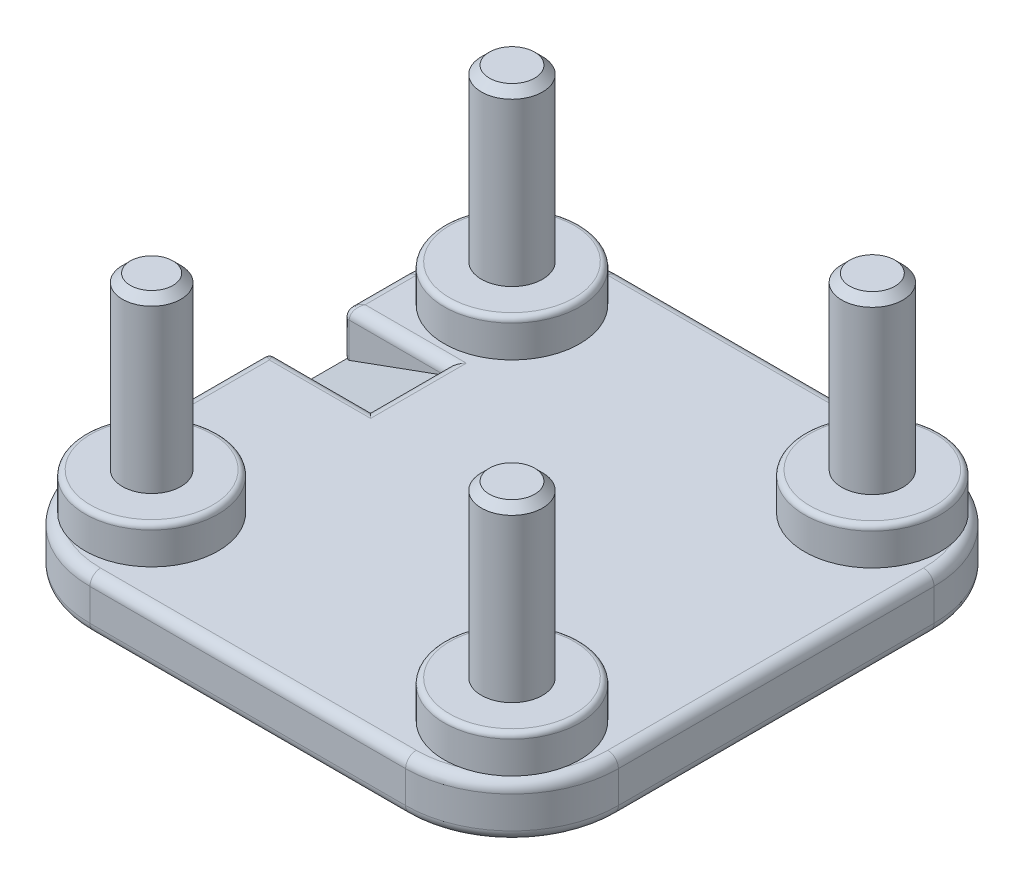
SolidWorks part; units mm, degrees
ref_plane "Front Plane" through (0, 0, 0) normal (0, 0, 1) x (1, 0, 0)
ref_plane "Top Plane" through (0, 0, 0) normal (0, 1, 0) x (1, 0, 0)
ref_plane "Right Plane" through (0, 0, 0) normal (1, 0, 0) x (0, 0, -1)
sketch "Sketch1" plane through (0, 0, 0) normal (0, 1, 0) x (1, 0, 0)
  line L1 (0.1721, 16.4036) -> (49.8471, 16.4036)
  line L2 (0.1721, 16.4036) -> (0.1721, 66.0786)
  line L3 (0.1721, 66.0786) -> (49.8471, 66.0786)
  line L4 (49.8471, 16.4036) -> (49.8471, 66.0786)
  line L8 (14.7548, 29.4959) -> (35.2548, 29.4959)
  line L9 (13.2548, 51.4959) -> (13.2548, 30.9959)
  line L10 (35.2548, 52.9959) -> (14.7548, 52.9959)
  line L11 (36.7548, 30.9959) -> (36.7548, 51.4959)
  line L12 (14.7548, 29.4959) -> (35.2548, 29.4959) construction
  line L13 (13.2548, 51.4959) -> (13.2548, 30.9959) construction
  line L14 (35.2548, 52.9959) -> (14.7548, 52.9959) construction
  line L15 (36.7548, 30.9959) -> (36.7548, 51.4959) construction
  line L16 (14.0048, 34.5935) -> (18.0048, 34.5935)
  line L17 (14.0048, 47.8007) -> (14.0048, 34.5935)
  line L18 (18.0048, 47.8007) -> (14.0048, 47.8007)
  line L19 (18.0048, 34.5935) -> (18.0048, 47.8007)
  line L20 (14.0048, 34.5935) -> (18.0048, 34.5935) construction
  line L21 (14.0048, 47.8007) -> (14.0048, 34.5935) construction
  line L22 (18.0048, 47.8007) -> (14.0048, 47.8007) construction
  line L23 (18.0048, 34.5935) -> (18.0048, 47.8007) construction
  line L24 (32.0048, 34.5935) -> (36.0048, 34.5935)
  line L25 (36.0048, 34.5935) -> (36.0048, 47.8007)
  line L26 (36.0048, 47.8007) -> (32.0048, 47.8007)
  line L27 (32.0048, 47.8007) -> (32.0048, 34.5935)
  line L28 (32.0048, 34.5935) -> (36.0048, 34.5935) construction
  line L29 (36.0048, 34.5935) -> (36.0048, 47.8007) construction
  line L30 (36.0048, 47.8007) -> (32.0048, 47.8007) construction
  line L31 (32.0048, 47.8007) -> (32.0048, 34.5935) construction
  line L32 (30.1074, 36.5249) -> (31.1807, 36.5249)
  line L33 (30.1074, 45.8309) -> (30.1074, 36.5249)
  line L34 (31.1807, 45.8309) -> (30.1074, 45.8309)
  line L35 (31.1807, 36.5249) -> (31.1807, 45.8309)
  line L36 (30.1074, 36.5249) -> (31.1807, 36.5249) construction
  line L37 (30.1074, 45.8309) -> (30.1074, 36.5249) construction
  line L38 (31.1807, 45.8309) -> (30.1074, 45.8309) construction
  line L39 (31.1807, 36.5249) -> (31.1807, 45.8309) construction
  line L40 (18.0048, 37.8287) -> (22.2111, 37.8287)
  line L41 (18.0048, 44.6472) -> (18.0048, 37.8287)
  line L42 (22.2111, 44.6472) -> (18.0048, 44.6472)
  line L43 (22.2111, 37.8287) -> (22.2111, 44.6472)
  line L44 (18.0048, 37.8287) -> (22.2111, 37.8287) construction
  line L45 (18.0048, 44.6472) -> (18.0048, 37.8287) construction
  line L46 (22.2111, 44.6472) -> (18.0048, 44.6472) construction
  line L47 (22.2111, 37.8287) -> (22.2111, 44.6472) construction
  line L48 (38.7548, 30.9959) -> (38.7548, 51.4959)
  line L49 (14.7548, 27.4959) -> (35.2548, 27.4959)
  line L50 (11.2548, 51.4959) -> (11.2548, 30.9959)
  line L51 (35.2548, 54.9959) -> (14.7548, 54.9959)
  line L52 (38.7548, 30.9959) -> (38.7548, 51.4959) construction
  line L53 (14.7548, 27.4959) -> (35.2548, 27.4959) construction
  line L54 (11.2548, 51.4959) -> (11.2548, 30.9959) construction
  line L55 (35.2548, 54.9959) -> (14.7548, 54.9959) construction
  circle A1 centre (8.0673, 58.1834) radius 6
  circle A2 centre (8.0673, 58.1834) radius 6 construction
  circle A3 centre (25.0048, 41.2459) radius 23
  circle A4 centre (25.0048, 41.2459) radius 23 construction
  circle A5 centre (8.0673, 58.1834) radius 3.125
  circle A6 centre (8.0673, 58.1834) radius 3.125 construction
  circle A7 centre (8.0673, 24.3084) radius 6
  circle A8 centre (8.0673, 24.3084) radius 6 construction
  circle A9 centre (8.0673, 24.3084) radius 3.125
  circle A10 centre (8.0673, 24.3084) radius 3.125 construction
  circle A11 centre (41.9423, 24.3084) radius 3.125
  circle A12 centre (41.9423, 24.3084) radius 3.125 construction
  circle A13 centre (41.9423, 24.3084) radius 6
  circle A14 centre (41.9423, 24.3084) radius 6 construction
  circle A15 centre (41.9423, 58.1834) radius 6
  circle A16 centre (41.9423, 58.1834) radius 6 construction
  circle A17 centre (41.9423, 58.1834) radius 3.125
  circle A18 centre (41.9423, 58.1834) radius 3.125 construction
  circle A19 centre (16.3548, 32.5959) radius 1.125
  circle A20 centre (16.3548, 32.5959) radius 1.125 construction
  circle A21 centre (33.6548, 32.5959) radius 1.125
  circle A22 centre (33.6548, 32.5959) radius 1.125 construction
  circle A23 centre (16.3548, 49.8959) radius 1.125
  circle A24 centre (16.3548, 49.8959) radius 1.125 construction
  circle A25 centre (33.6548, 49.8959) radius 1.125
  arc A26 (13.2548, 30.9959) -> (14.7548, 29.4959) centre (14.7548, 30.9959) ccw
  arc A27 (14.7548, 52.9959) -> (13.2548, 51.4959) centre (14.7548, 51.4959) ccw
  arc A28 (36.7548, 51.4959) -> (35.2548, 52.9959) centre (35.2548, 51.4959) ccw
  arc A29 (35.2548, 29.4959) -> (36.7548, 30.9959) centre (35.2548, 30.9959) ccw
  arc A30 (13.2548, 30.9959) -> (14.7548, 29.4959) centre (14.7548, 30.9959) ccw construction
  arc A31 (14.7548, 52.9959) -> (13.2548, 51.4959) centre (14.7548, 51.4959) ccw construction
  arc A32 (36.7548, 51.4959) -> (35.2548, 52.9959) centre (35.2548, 51.4959) ccw construction
  arc A33 (35.2548, 29.4959) -> (36.7548, 30.9959) centre (35.2548, 30.9959) ccw construction
  circle A34 centre (33.6548, 49.8959) radius 1.125 construction
  arc A38 (38.7548, 51.4959) -> (35.2548, 54.9959) centre (35.2548, 51.4959) ccw
  arc A39 (35.2548, 27.4959) -> (38.7548, 30.9959) centre (35.2548, 30.9959) ccw
  arc A40 (11.2548, 30.9959) -> (14.7548, 27.4959) centre (14.7548, 30.9959) ccw
  arc A41 (14.7548, 54.9959) -> (11.2548, 51.4959) centre (14.7548, 51.4959) ccw
  arc A42 (38.7548, 51.4959) -> (35.2548, 54.9959) centre (35.2548, 51.4959) ccw construction
  arc A43 (35.2548, 27.4959) -> (38.7548, 30.9959) centre (35.2548, 30.9959) ccw construction
  arc A44 (11.2548, 30.9959) -> (14.7548, 27.4959) centre (14.7548, 30.9959) ccw construction
  arc A45 (14.7548, 54.9959) -> (11.2548, 51.4959) centre (14.7548, 51.4959) ccw construction
  dimension "D20" = 7.9048
  dimension "D21" = 7.9048
  dimension "D22" = 49.675
  dimension "D23" = 49.675
  dimension "D24" = 49.675
  dimension "D1" = 0
  dimension "D2" = 0
  dimension "D3" = 0
  dimension "D4" = 0
  dimension "D5" = 0
  dimension "D6" = 0
  dimension "D7" = 0
  dimension "D8" = 0
  dimension "D9" = 0
  dimension "D10" = 0
  dimension "D11" = 0
  dimension "D12" = 0
  dimension "D13" = 0
  dimension "D14" = 0
  dimension "D15" = 0
  dimension "D16" = 0
  dimension "D17" = 0
  dimension "D18" = 0
  dimension "D19" = 0
extrude "Boss-Extrude1" add sketch "Sketch1" along normal blind 5
sketch "Sketch3" plane through (0, 0, 0) normal (0, 1, 0) x (1, 0, 0)
  circle A0 centre (8.0673, 58.1834) radius 4
  circle A1 centre (41.9423, 58.1834) radius 4
  circle A2 centre (41.9423, 24.3084) radius 4
  circle A3 centre (8.0673, 24.3084) radius 4
  circle A4 centre (8.0673, 24.3084) radius 4.275
  circle A5 centre (41.9423, 24.3084) radius 4.275
  circle A6 centre (41.9423, 58.1834) radius 4.275
  circle A7 centre (8.0673, 58.1834) radius 4.275
  dimension "D1" = 8
  dimension "D2" = 8
  dimension "D3" = 8
  dimension "D4" = 8
  dimension "D5" = 8.55
  dimension "D6" = 8.55
  dimension "D7" = 8.55
  dimension "D8" = 8.55
extrude "Cut-Extrude1" cut sketch "Sketch3" along normal up to next from offset 1 contours A5 | A6 | A4 | A7
sketch "Sketch2" plane through (0, 0, 0) normal (0, 1, 0) x (1, 0, 0)
  line L0 (17.374, 45.7096) -> (5.2059, 45.7096) construction
  circle A4 centre (41.9423, 58.1834) radius 2.875
  circle A5 centre (41.9423, 24.3084) radius 2.875
  circle A6 centre (8.0673, 24.3084) radius 2.75
  circle A7 centre (8.0673, 58.1834) radius 2.875
  circle A8 centre (41.9423, 58.1834) radius 6.375
  circle A9 centre (41.9423, 24.3084) radius 6.375
  circle A10 centre (8.0673, 24.3084) radius 6.25
  circle A11 centre (8.0673, 58.1834) radius 6.375
  dimension "D2" = 5.75
  dimension "D3" = 5.75
  dimension "D4" = 5.5
  dimension "D5" = 5.75
  dimension "D1" = 3.5
extrude "Boss-Extrude2" add sketch "Sketch2" along normal blind 3.5 from surface separate body contours A11 | A10 | A9 | A8 starting at face at (41.9423, 5, -62.4584)
extrude "Boss-Extrude3" add sketch "Sketch2<3>" along normal blind 16 from surface contours A7 | A4 | A5 | A6 region at (41.9423, 0, -58.1834) region at (41.9423, 0, -24.3084) region at (8.0673, 0, -24.3084) region at (8.0673, 0, -58.1834) starting at face at (8.0673, 8.5, -64.5584)
sketch "Sketch2<3>" plane through (0, 0, 0) normal (0, 1, 0) x (1, 0, 0) same geometry as "Sketch2"
extrude "Boss-Extrude4" add sketch "Sketch3<2>" against normal blind 1.875 from surface contours A0 | A3 | A1 | A2 starting at face at (8.0673, 5, -30.5584)
sketch "Sketch3<2>" plane through (0, 0, 0) normal (0, 1, 0) x (1, 0, 0) same geometry as "Sketch3"
sketch "Sketch4" plane through (0, 5, 0) normal (0, 1, 0) x (1, 0, 0)
  line L0 (2.0944, 43.2738) -> (9.6849, 43.2738) construction
  line L1 (9.6849, 43.2738) -> (9.6849, 50.2738) construction
  line L2 (9.6849, 50.2738) -> (3.7847, 50.2738) construction
  line L3 (2.0944, 43.2738) -> (9.6849, 43.2738)
  line L4 (9.6849, 43.2738) -> (9.6849, 50.2738)
  line L5 (9.6849, 50.2738) -> (3.7847, 50.2738)
  line L6 (3.7847, 50.2738) -> (-1.6497, 50.2738)
  line L7 (-1.6497, 50.2738) -> (-1.6497, 43.2738)
  line L8 (-1.6497, 43.2738) -> (2.0944, 43.2738)
extrude "Cut-Extrude2" cut sketch "Sketch4" against normal blind 1
draft "Draft1" type of draft neutral plane draft angle 20 faces to draft 1 face at (4.9285, 4, -46.7738) neutral plane through (9.6849, 4, -43.2738) neutral plane normal (-1, 0, 0) parameters "D1"=20
chamfer "Chamfer1" distance 0.75 angle 45 4 edges at (41.9423, 5, -62.4584) (41.9423, 5, -28.5834) (8.0673, 5, -28.5834) (8.0673, 5, -62.4584)
fillet "Fillet5" radius 10 4 edges at (49.8471, 2.5, -16.4036) (49.8471, 2.5, -66.0786) (0.1721, 2.5, -66.0786) (0.1721, 2.5, -16.4036)
fillet "Fillet6" radius 1 20 edges at (3.101, 0, -19.3325) (0.1721, 0, -41.2411) (3.101, 0, -63.1496) (25.0096, 0, -66.0786) (46.9182, 0, -63.1496) (49.8471, 0, -41.2411) (46.9182, 0, -19.3325) (3.101, 5, -19.3325) (0.1721, 5, -53.1762) (0.1721, 5, -34.8387) (3.101, 5, -63.1496) (25.0096, 5, -66.0786) (46.9182, 5, -63.1496) (49.8471, 5, -41.2411) (46.9182, 5, -19.3325) (25.0096, 0, -16.4036) (25.0096, 5, -16.4036) (9.6849, 5, -46.7738) (4.9285, 5, -43.2738) (4.9285, 5, -50.2738)
fillet "Fillet1" radius 0.5 1 edges at (8.0673, 8.5, -30.5584)
fillet "Fillet2" radius 0.5 1 edges at (41.9423, 8.5, -30.6834)
fillet "Fillet3" radius 0.5 1 edges at (8.0673, 8.5, -64.5584)
fillet "Fillet4" radius 0.5 1 edges at (41.9423, 8.5, -64.5584)
chamfer "Chamfer2" distance 0.75 angle 45 1 edges at (8.0673, 24.5, -27.0584)
chamfer "Chamfer3" distance 0.75 angle 45 1 edges at (8.0673, 24.5, -61.0584)
chamfer "Chamfer4" distance 0.75 angle 45 1 edges at (41.9423, 24.5, -61.0584)
chamfer "Chamfer5" distance 0.75 angle 45 1 edges at (41.9423, 24.5, -27.1834)
fillet "Fillet7" radius 0.5 6 edges at (0.465, 4.7071, -42.9809) (0.1964, 0.781, -43.2738) (0.1964, 0.781, -50.2738) (0.465, 4.7071, -50.5667) (0.1721, 2.5, -43.2738) (0.1721, 2.5, -50.2738)
